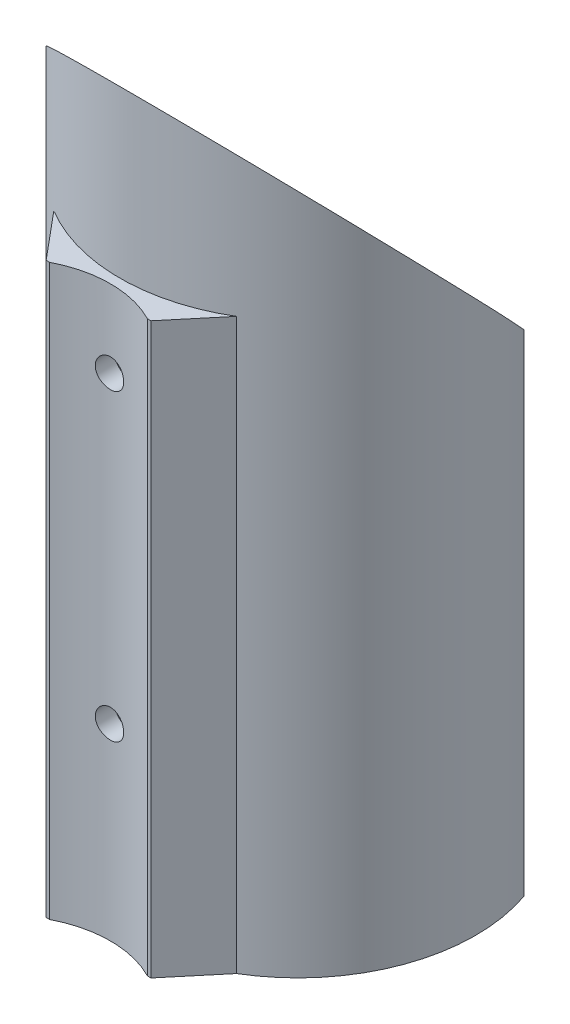
SolidWorks part; units mm, degrees
ref_plane "Front Plane" through (0, 0, 0) normal (0, 0, 1) x (1, 0, 0)
ref_plane "Top Plane" through (0, 0, 0) normal (0, 1, 0) x (1, 0, 0)
ref_plane "Right Plane" through (0, 0, 0) normal (1, 0, 0) x (0, 0, -1)
sketch "Sketch1" plane through (0, 0, 0) normal (0, 1, 0) x (1, 0, 0)
  circle A0 centre (0, 0) radius 32.5
  circle A1 centre (0, 0) radius 37.5
  dimension "D1" = 65
  dimension "D2" = 5
extrude "Boss-Extrude1" add sketch "Sketch1" along normal blind 150
sketch "Sketch2" plane through (0, 0, 0) normal (0, -1, 0) x (1, 0, 0)
  circle A0 centre (0, 0) radius 37.5
extrude "Boss-Extrude2" add sketch "Sketch2" along normal blind 5
ref_plane "Plane1" through (50, 0, 0) normal (1, 0, 0) x (0, 0, -1)
sketch "Sketch3" plane through (50, 0, 0) normal (1, 0, 0) x (0, 0, -1)
  line L0 (-37.5, 150) -> (37.5, 72.5)
  line L1 (37.5, -5) -> (37.5, 150) construction
  line L2 (37.5, 72.5) -> (37.5, 150)
  line L3 (37.5, 150) -> (-37.5, 150)
extrude "Cut-Extrude1" cut sketch "Sketch3" against normal blind 115
ref_plane "Plane2" through (0, 0, 42) normal (0, 0, 1) x (1, 0, 0)
sketch "Sketch4" plane through (0, 0, 42) normal (0, 0, 1) x (1, 0, 0)
  line L0 (-37.5, -5) -> (37.5, -5) construction
  line L1 (-10, -5) -> (10, -5)
  line L2 (-10, -5) -> (-10, 115)
  line L3 (-10, 115) -> (10, 115)
  line L4 (10, -5) -> (10, 115)
  point P6 (0, -5)
  dimension "D1" = 120
  dimension "D2" = 20
  dimension "D3" = 0
extrude "Boss-Extrude3" add sketch "Sketch4" against normal blind 9
sketch "Sketch5" plane through (0, 0, 42) normal (0, 0, 1) x (1, 0, 0)
  circle A0 centre (0, 98.657) radius 3
  circle A1 centre (0, 34.657) radius 3
  dimension "D1" = 6
  dimension "D2" = 6
  dimension "D3" = 64
extrude "Cut-Extrude2" cut sketch "Sketch5" against normal blind 119
chamfer "Chamfer1" distance 9 angle 45 2 edges at (10, 55, 36.1421) (-10, 55, 36.1421) first distance on face at (10, 55, 39.071) first distance on face at (-10, 55, 39.071)
sketch "Sketch6" plane through (0, 115, 0) normal (0, 1, 0) x (1, 0, 0)
  line L0 (-41.25, -42) -> (41.25, -42) construction
  circle A0 centre (0, -62) radius 22.5
  dimension "D1" = 45
  dimension "D2" = 20
extrude "Cut-Extrude3" cut sketch "Sketch6" against normal blind 129
sketch "Sketch7" plane through (0, 0, 0) normal (0, 1, 0) x (1, 0, 0)
  line L0 (-32.5, 0) -> (32.5, 0)
  arc A0 (-32.5, 0) -> (32.5, 0) centre (0, 0) ccw
  circle A1 centre (0, 0) radius 32.5 construction
  dimension "D2" = 0
  dimension "D1" = 0
extrude "Cut-Extrude4" cut sketch "Sketch7" against normal blind 129
fillet "Fillet1" radius 3 2 edges at (-32.5, -2.5, 0) (32.5, -2.5, 0)
ref_plane "Plane3" through (0, 0, -40) normal (0, 0, 1) x (1, 0, 0)
sketch "Sketch8" plane through (0, 0, -40) normal (0, 0, 1) x (1, 0, 0)
  circle A0 centre (0, 98.657) radius 5
  circle A1 centre (0, 34.657) radius 5
  dimension "D1" = 10
  dimension "D2" = 10
extrude "Cut-Extrude5" cut sketch "Sketch8" along normal blind 75.5
sketch "Sketch9" plane through (50, 0, 0) normal (1, 0, 0) x (0, 0, -1)
  line L1 (37.5, -5) -> (17.5, -5)
  line L2 (37.5, -5) -> (37.5, 142.7348)
  line L3 (37.5, 142.7348) -> (17.5, 142.7348)
  line L4 (17.5, -5) -> (17.5, 142.7348)
  dimension "D1" = 20
extrude "Cut-Extrude6" cut sketch "Sketch9" against normal blind 85
chamfer "Chamfer2" distance 3 angle 45 2 edges at (33.1662, 44.0833, -17.5) (-33.1662, 44.0833, -17.5) first distance on face at (0, 45.3333, -17.5)
fillet "Fillet2" radius 5 1 edges at (0, 144.8333, 32.5)
